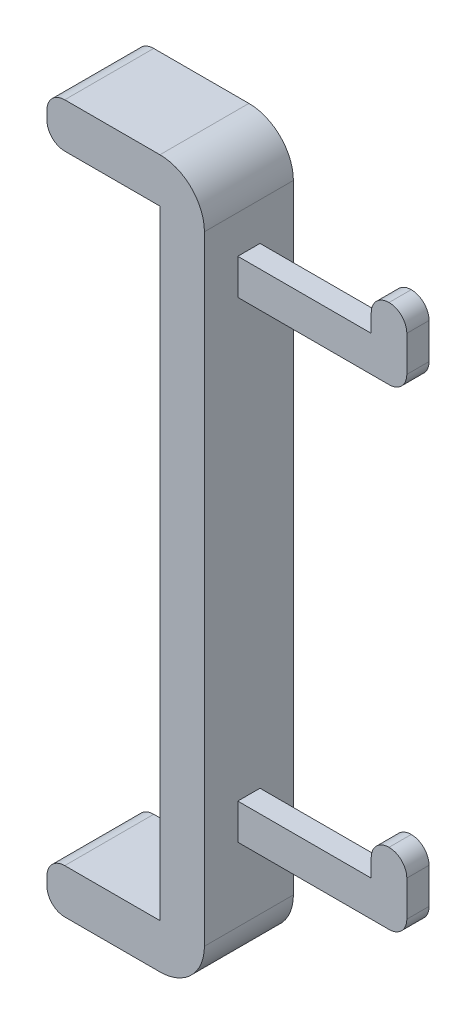
SolidWorks part; units mm, degrees
ref_plane "Front Plane" through (0, 0, 0) normal (0, 0, 1) x (1, 0, 0)
ref_plane "Top Plane" through (0, 0, 0) normal (0, 1, 0) x (1, 0, 0)
ref_plane "Right Plane" through (0, 0, 0) normal (1, 0, 0) x (0, 0, -1)
sketch "Sketch1" plane through (0, 0, 0) normal (0, 0, 1) x (1, 0, 0)
  line L0 (-57.9104, 56.7282) -> (-22.5104, 56.7282)
  line L2 (-22.5104, -102.3718) -> (-57.9104, -102.3718)
  line L3 (-57.9104, -102.3718) -> (-57.9104, -92.3718)
  line L4 (-57.9104, -92.3718) -> (-32.5104, -92.3718)
  line L5 (-32.5104, -92.3718) -> (-32.5104, 46.7282)
  line L6 (-32.5104, 46.7282) -> (-57.9104, 46.7282)
  line L7 (-57.9104, 46.7282) -> (-57.9104, 56.7282)
  line L10 (-22.5104, -75.8551) -> (-22.5104, -102.3718)
  line L23 (-22.5104, -75.8551) -> (-22.5104, -49.3384)
  line L24 (-22.5104, -49.3384) -> (-22.5104, -22.8218)
  line L25 (-22.5104, -22.8218) -> (-22.5104, 3.6949)
  line L26 (-22.5104, 3.6949) -> (-22.5104, 30.2116)
  line L27 (-22.5104, 30.2116) -> (-22.5104, 56.7282)
  line L28 (-22.5104, 30.2116) -> (15.4896, 30.2116)
  line L29 (15.4896, 30.2116) -> (15.4896, 46.2116)
  line L30 (15.4896, 46.2116) -> (7.4896, 46.2116)
  line L31 (7.4896, 46.2116) -> (7.4896, 38.2116)
  line L32 (7.4896, 38.2116) -> (-22.5104, 38.2116)
  line L33 (-22.5104, 38.2116) -> (-22.5104, 30.2116)
  line L34 (-22.5104, -75.8551) -> (15.4896, -75.8551)
  line L35 (15.4896, -75.8551) -> (15.4896, -59.8551)
  line L36 (15.4896, -59.8551) -> (7.4896, -59.8551)
  line L37 (7.4896, -59.8551) -> (7.4896, -67.8551)
  line L38 (7.4896, -67.8551) -> (-22.5104, -67.8551)
  line L39 (-22.5104, -67.8551) -> (-22.5104, -75.8551)
  dimension "D1" = 139.1
  dimension "D2" = 25.4
  dimension "D3" = 25.4
  dimension "D4" = 10
  dimension "D5" = 10
  dimension "D6" = 35.4
  dimension "D7" = 30
  dimension "D8" = 8
  dimension "D9" = 8
  dimension "D10" = 16
  dimension "D11" = 8
  dimension "D12" = 16
  dimension "D13" = 30
  dimension "D14" = 8
extrude "Boss-Extrude1" add sketch "Sketch1" along normal blind 10 and the other way blind 10 contours L26 L27 L0 L7 L6 L5 L4 L3 L2 L10 L23 L24 L25 region at (-31.7941, -22.8218, 0)
extrude "Boss-Extrude2" add sketch "Sketch1<3>" along normal blind 2.5 and the other way blind 2.5 contours L31 L32 L27 L28 L29 L30 | L37 L38 L23 L34 L35 L36 region at (-0.9017, 35.6029, 0) region at (-0.9017, -70.4638, 0)
sketch "Sketch1<3>" plane through (0, 0, 0) normal (0, 0, 1) x (1, 0, 0) same geometry as "Sketch1"
fillet "Fillet1" radius 10 2 edges at (-22.5104, 56.7282, 0) (-22.5104, -102.3718, 0)
fillet "Fillet2" radius 4 9 edges at (-57.9104, -102.3718, 0) (-57.9104, -92.3718, 0) (7.4896, -59.8551, 0) (15.4896, -59.8551, 0) (15.4896, -75.8551, 0) (7.4896, 46.2116, 0) (15.4896, 46.2116, 0) (15.4896, 30.2116, 0) (-57.9104, 56.7282, 0)
fillet "Fillet3" radius 4 1 edges at (-57.9104, 46.7282, 0)
